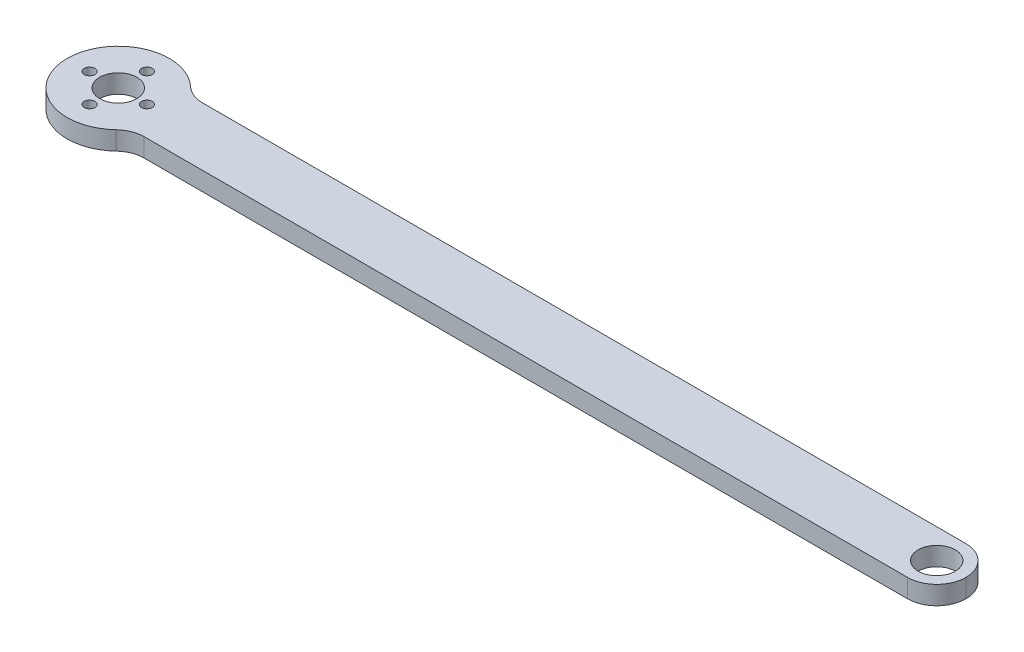
SolidWorks part; units mm, degrees
material "ABS"
ref_plane "Front Plane" through (0, 0, 0) normal (0, 0, 1) x (1, 0, 0)
ref_plane "Top Plane" through (0, 0, 0) normal (0, 1, 0) x (1, 0, 0)
ref_plane "Right Plane" through (0, 0, 0) normal (1, 0, 0) x (0, 0, -1)
sketch "Sketch1" plane through (0, 0, 0) normal (0, 1, 0) x (1, 0, 0)
  line L1 (-150, 10) -> (150, 10)
  line L2 (-150, 10) -> (-150, -10)
  line L3 (-150, -10) -> (150, -10)
  line L4 (150, 10) -> (150, -10)
  point P4 (0, -10)
  point P5 (0, 10)
  point P9 (150, 0)
  dimension "D1" = 300
  dimension "D2" = 20
extrude "Boss-Extrude1" add sketch "Sketch1" along normal blind 6.35
sketch "Sketch2" plane through (0, 0, 0) normal (0, -1, 0) x (-1, 0, 0)
  line L0 (-3.4925, 0) -> (3.4925, 0) construction
  line L1 (150, 10) -> (150, -10) construction
  circle A0 centre (140, 0) radius 6.35
  dimension "D1" = 12.7
  dimension "D2" = 10
extrude "Cut-Extrude1" cut sketch "Sketch2" against normal up to surface (6.35 mm away) up to face at (0, 6.35, 0)
mirror "Mirror1" about plane through (0, 0, 0) normal (1, 0, 0) of "Cut-Extrude1"
fillet "Congé1" radius 10 4 edges at (-150, 3.175, -10) (-150, 3.175, 10) (150, 3.175, -10) (150, 3.175, 10)
sketch "Sketch3" plane through (0, 6.35, 0) normal (0, 1, 0) x (1, 0, 0)
  circle A0 centre (-140, 0) radius 17.5
  circle A3 centre (-140, 0) radius 6.35 construction
  circle A4 centre (-140, 0) radius 6.35
  dimension "D2" = 35
extrude "Boss-Extrude2" add sketch "Sketch3" against normal up to surface (6.35 mm away) up to face at (140, 0, -6.35)
fillet "Fillet1" radius 10 2 edges at (-125.6386, 3.175, -10) (-125.6386, 3.175, 10)
sketch "Sketch5" plane through (0, 6.35, 0) normal (0, 1, 0) x (1, 0, 0)
  circle A0 centre (-140, 9.779) radius 1.83
  circle A1 centre (-130.221, 0) radius 1.83
  circle A2 centre (-140, -9.779) radius 1.83
  circle A3 centre (-149.779, 0) radius 1.83
  point P12 (-140, 0)
  dimension "D1" = 3.66
  dimension "D2" = 4
extrude "Cut-Extrude2" cut sketch "Sketch5" against normal blind 10
